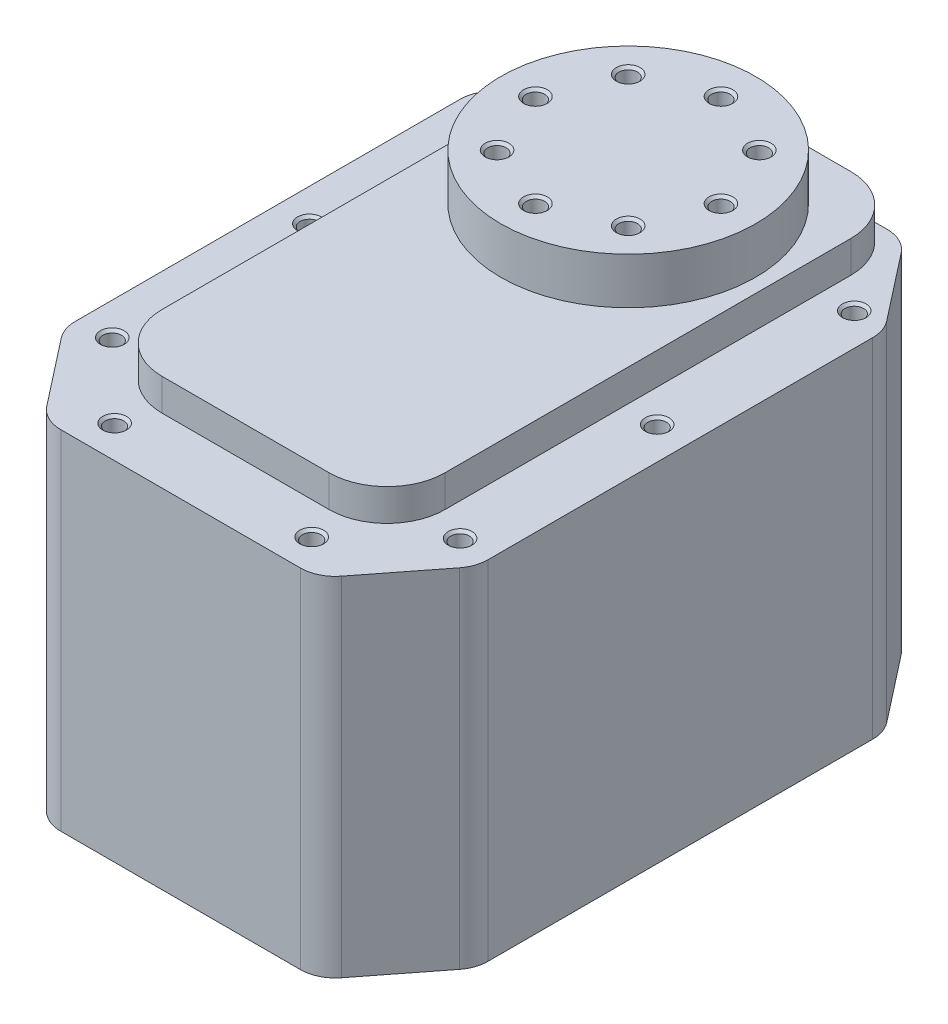
SolidWorks part; units mm, degrees
ref_plane "Front Plane" through (0, 0, 0) normal (0, 0, 1) x (1, 0, 0)
ref_plane "Top Plane" through (0, 0, 0) normal (0, 1, 0) x (1, 0, 0)
ref_plane "Right Plane" through (0, 0, 0) normal (1, 0, 0) x (0, 0, -1)
sketch "Sketch1" plane through (0, 0, 0) normal (0, 1, 0) x (1, 0, 0)
  line L0 (0, 12) -> (0, 0) construction
  line L1 (-12.2, 12) -> (12.2, 12)
  line L2 (-12.2, 12) -> (-12.2, -33)
  line L3 (-12.2, -33) -> (12.2, -33)
  line L4 (12.2, 12) -> (12.2, -33)
  dimension "D1" = 12
  dimension "D2" = 45
  dimension "D3" = 24.4
extrude "Boss-Extrude1" add sketch "Sketch1" against normal blind 35.5
fillet "Fillet1" radius 5 4 edges at (12.2, -17.75, 33) (-12.2, -17.75, 33) (-12.2, -17.75, -12) (12.2, -17.75, -12)
ref_plane "Plane1" through (0, -17.75, 0) normal (0, 1, 0) x (1, 0, 0)
sketch "Sketch2" plane through (0, -17.75, 0) normal (0, 1, 0) x (1, 0, 0)
  line L0 (7.2, 12) -> (-7.2, 12) construction
  line L1 (-17.8, 12) -> (17.8, 12)
  line L2 (-17.8, 12) -> (-17.8, -38.6)
  line L3 (-17.8, -38.6) -> (17.8, -38.6)
  line L4 (17.8, 12) -> (17.8, -38.6)
  line L5 (0, 12) -> (0, 0) construction
  dimension "D1" = 35.6
  dimension "D2" = 50.6
extrude "Boss-Extrude2" add sketch "Sketch2" along normal mid plane 30
chamfer "Chamfer2" distance 6 angle 52 4 edges at (17.8, -17.75, 38.6) (-17.8, -17.75, 38.6) (17.8, -17.75, -12) (-17.8, -17.75, -12) first distance on face at (0, -17.75, 38.6) first distance on face at (0, -17.75, -12)
fillet "Fillet2" radius 3 8 edges at (-11.8, -17.75, 38.6) (-17.8, -17.75, 30.9204) (11.8, -17.75, 38.6) (17.8, -17.75, 30.9204) (17.8, -17.75, -4.3204) (11.8, -17.75, -12) (-17.8, -17.75, -4.3204) (-11.8, -17.75, -12)
sketch "Sketch3" plane through (0, 0, 0) normal (0, 1, 0) x (1, 0, 0)
  circle A0 centre (0, 0) radius 11
  dimension "D1" = 22
extrude "Boss-Extrude3" add sketch "Sketch3" along normal blind 4
extrude "Boss-Extrude5" add sketch "Sketch3<3>" against normal blind 2.5 from surface starting at face at (0, -35.5, 10.5)
sketch "Sketch3<3>" plane through (0, 0, 0) normal (0, 1, 0) x (1, 0, 0) same geometry as "Sketch3"
hole_wizard "M2x0.4 Tapped Hole1" positions "Sketch5" profile "Sketch6" tap size "M2x0.4" standard "ANSI Metric" end condition through all
sketch "Sketch5" plane through (0, 4, 0) normal (0, 1, 0) x (1, 0, 0)
  line L0 (0, 0) -> (0, 8) construction
  line L3 (0, 0) -> (0, -8) construction
  circle A0 centre (0, 0) radius 8 construction
  point P5 (0, 8)
  point P19 (5.6569, 5.6569)
  point P20 (8, 0)
  point P21 (5.6569, -5.6569)
  point P22 (0, -8)
  point P23 (-5.6569, -5.6569)
  point P24 (-8, 0)
  point P25 (-5.6569, 5.6569)
  dimension "D1" = 16
  dimension "D2" = 8
cosmetic thread "Hole Thread1"
cosmetic thread "Hole Thread2"
cosmetic thread "Hole Thread3"
cosmetic thread "Hole Thread4"
cosmetic thread "Hole Thread5"
cosmetic thread "Hole Thread6"
cosmetic thread "Hole Thread7"
cosmetic thread "Hole Thread8"
sketch "Sketch6" plane through (-5.6569, 4, -5.6569) normal (1, 0, 0) x (0, 0, 1)
  line L0 (0, 0) -> (0, 42)
  line L1 (0, 42) -> (0.8, 42)
  line L2 (0.8, 42) -> (0.8, 0.225)
  line L3 (0.8, 0.225) -> (1.025, 0)
  line L5 (1.025, 0) -> (0, 0)
  line L6 (-0.8, 0.225) -> (-1.025, 0) construction
  line L11 (0, -6.35) -> (0, 107.95) construction
  dimension "Thru Tap Drill Dia." = 1.6
  dimension "Thru Tap Drill Depth" = 42
  dimension "Near C'Sink Dia." = 2.05
  dimension "Near C'Sink Angle" = 90
ref_axis "Motor Axis" through (0, 4, 0) along (0, -1, 0)
hole_wizard "M2x0.4 Tapped Hole2" positions "Sketch8" profile "Sketch9" tap size "M2x0.4" standard "ANSI Metric" end condition through all
sketch "Sketch8" plane through (0, -2.75, 0) normal (0, 1, 0) x (1, 0, 0)
  line L0 (-15, 7.9042) -> (-15, -35.8) construction
  line L1 (-15, -35.8) -> (15, -35.8) construction
  line L2 (15, -35.8) -> (15, 7.9042) construction
  line L5 (0, -35.8) -> (0, 0) construction
  line L7 (-12.7008, 10.847) -> (-17.164, 5.1344) construction
  line L8 (17.164, 5.1344) -> (12.7008, 10.847) construction
  point P20 (-15, 4.5)
  point P23 (-15, -12.5)
  point P25 (-15, -29.5)
  point P27 (-8.5, -35.8)
  point P30 (8.5, -35.8)
  point P31 (15, -29.5)
  point P32 (15, -12.5)
  point P33 (15, 4.5)
  dimension "D1" = 30
  dimension "D2" = 35.8
  dimension "D3" = 4.5
  dimension "D4" = 17
  dimension "D5" = 17
  dimension "D6" = 8.5
sketch "Sketch9" plane through (15, -2.75, -4.5) normal (1, 0, 0) x (0, 0, 1)
  line L0 (0, 0) -> (0, 35.25)
  line L1 (0, 35.25) -> (0.8, 35.25)
  line L2 (0.8, 35.25) -> (0.8, 0.225)
  line L3 (0.8, 0.225) -> (1.025, 0)
  line L5 (1.025, 0) -> (0, 0)
  line L6 (-0.8, 0.225) -> (-1.025, 0) construction
  line L11 (0, -6.35) -> (0, 107.95) construction
  dimension "Thru Tap Drill Dia." = 1.6
  dimension "Thru Tap Drill Depth" = 35.25
  dimension "Near C'Sink Dia." = 2.05
  dimension "Near C'Sink Angle" = 90
cosmetic thread "Hole Thread9"
cosmetic thread "Hole Thread10"
cosmetic thread "Hole Thread11"
cosmetic thread "Hole Thread12"
cosmetic thread "Hole Thread13"
cosmetic thread "Hole Thread14"
cosmetic thread "Hole Thread15"
cosmetic thread "Hole Thread16"
